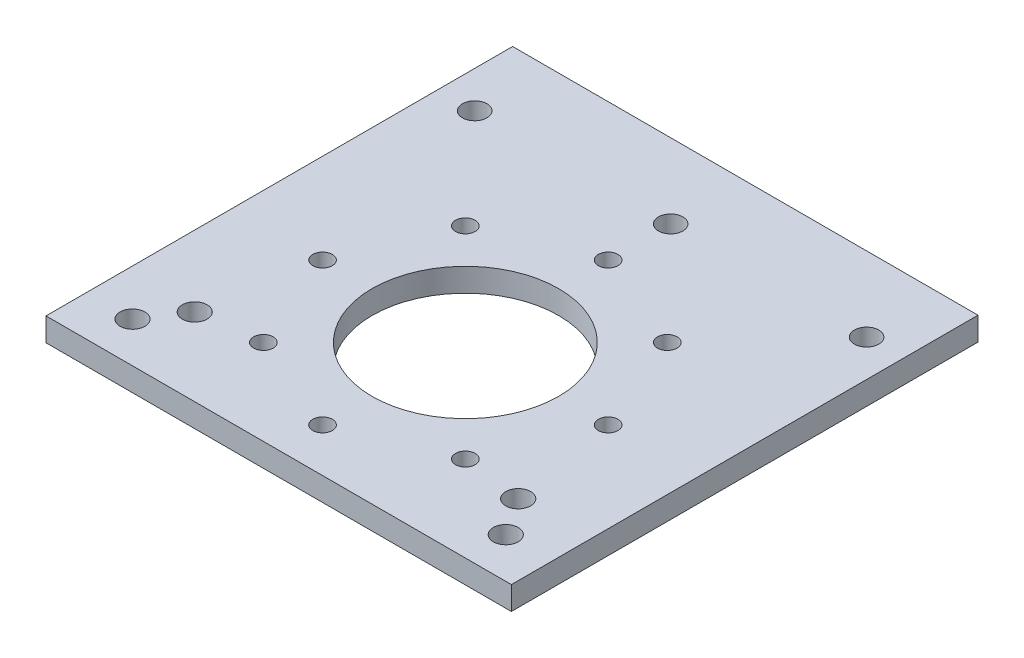
SolidWorks part; units mm, degrees
material "6061 Alloy"
ref_plane "Front Plane" through (0, 0, 0) normal (0, 0, 1) x (1, 0, 0)
ref_plane "Top Plane" through (0, 0, 0) normal (0, 1, 0) x (1, 0, 0)
ref_plane "Right Plane" through (0, 0, 0) normal (1, 0, 0) x (0, 0, -1)
sketch "Sketch2" plane through (0, 0, 0) normal (0, 1, 0) x (1, 0, 0)
  line L0 (0, 0) -> (0, 34.925) construction
  line L1 (-47.5, -60.325) -> (-47.5, 34.925)
  line L2 (47.5, -60.325) -> (47.5, 34.925)
  line L3 (-47.5, 34.925) -> (47.5, 34.925)
  line L4 (-47.5, -60.325) -> (47.5, -60.325)
  point P3 (47.5, -12.7)
  point P5 (0, 34.925)
  point P12 (0, -60.325)
  dimension "D1" = 95.25
  dimension "D2" = 95
  dimension "D3" = 12.7
extrude "Boss-Extrude3" add sketch "Sketch2" along normal blind 4.7625
sketch "Sketch3" plane through (0, 4.7625, 0) normal (0, 1, 0) x (1, 0, 0)
  line L0 (47.5, 34.925) -> (-47.5, 34.925) construction
  circle A1 centre (0, -22.225) radius 19.05
  dimension "D2" = 38.1
  dimension "D3" = 57.15
extrude "Cut-Extrude1" cut sketch "Sketch3" against normal through all
sketch "Sketch4" plane through (0, 4.7625, 0) normal (0, 1, 0) x (1, 0, 0)
  line L0 (47.5, 34.925) -> (-47.5, 34.925) construction
  line L1 (0, 34.925) -> (0, 55.3884) construction
  point P0 (-40, 19.685)
  point P7 (40, 19.685)
  point P8 (0, 19.685)
  point P10 (0, 19.685)
  dimension "D1" = 15.24
  dimension "D2" = 80
hole_wizard "M6x1.0 Tapped Hole1" positions "Sketch4" profile "Sketch6" tap size "M6x1.0" standard "ANSI Metric"
sketch "Sketch6" plane through (-40, 4.7625, -19.685) normal (1, 0, 0) x (0, 0, 1)
  line L0 (0, 0) -> (0, 6.2647)
  line L1 (0, 6.2647) -> (2.5, 4.7625)
  line L2 (2.5, 4.7625) -> (2.5, 0)
  line L5 (2.5, 0) -> (0, 0)
  line L10 (0, 6.2647) -> (-2.5, 4.7625) construction
  line L11 (0, -6.35) -> (0, 107.95) construction
  dimension "Tap Drill Dia." = 5
  dimension "Tap Drill Depth" = 4.7625
  dimension "Drill Angle" = 118
sketch "Sketch7" plane through (0, 4.7625, 0) normal (0, 1, 0) x (1, 0, 0)
  line L0 (0, 0) -> (0, -60.325) construction
  line L1 (-47.5, -60.325) -> (47.5, -60.325) construction
  circle A0 centre (-33.02, -44.45) radius 2.54
  circle A1 centre (33.02, -44.45) radius 2.54
  circle A2 centre (-38.1, -52.07) radius 2.54
  circle A3 centre (38.1, -52.07) radius 2.54
  dimension "D3" = 5.08
  dimension "D4" = 5.08
  dimension "D6" = 38.1
  dimension "D1" = 44.45
  dimension "D2" = 33.02
  dimension "D5" = 7.62
extrude "Cut-Extrude2" cut sketch "Sketch7" against normal blind 7.62
sketch "Sketch12" plane through (0, 4.7625, 0) normal (0, 1, 0) x (1, 0, 0)
  line L0 (47.5, 34.925) -> (-47.5, 34.925) construction
  circle A0 centre (0, -22.225) radius 29.1465
  circle A1 centre (0, 6.9215) radius 2
  circle A2 centre (20.6097, -1.6153) radius 2
  circle A3 centre (29.1465, -22.225) radius 2
  circle A4 centre (20.6097, -42.8347) radius 2
  circle A5 centre (0, -51.3715) radius 2
  circle A6 centre (-20.6097, -42.8347) radius 2
  circle A7 centre (-29.1465, -22.225) radius 2
  circle A8 centre (-20.6097, -1.6153) radius 2
  point P25 (0, -22.225)
  dimension "D1" = 4
  dimension "D2" = 58.293
  dimension "D3" = 57.15
  dimension "D4" = 8
extrude "Cut-Extrude3" cut sketch "Sketch12" against normal through all contours A8 | A7 | A6 | A5 | A4 | A3 | A2 | A1
